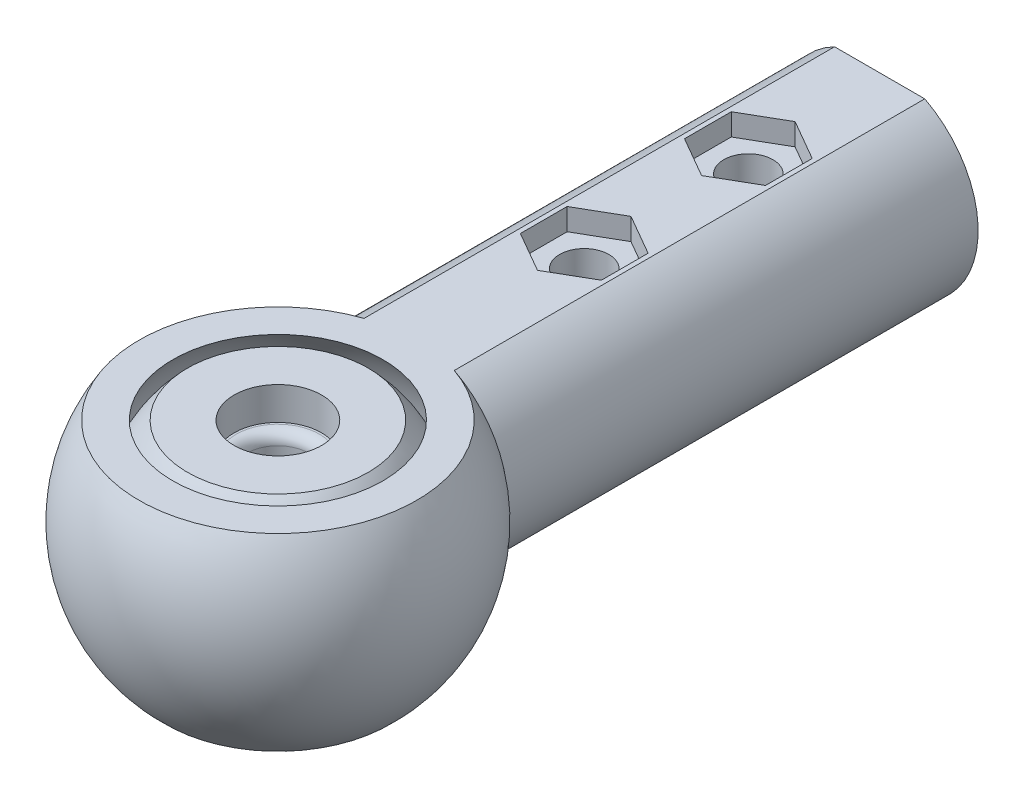
SolidWorks part; units mm, degrees
ref_plane "Front Plane" through (0, 0, 0) normal (0, 0, 1) x (1, 0, 0)
ref_plane "Top Plane" through (0, 0, 0) normal (0, 1, 0) x (1, 0, 0)
ref_plane "Right Plane" through (0, 0, 0) normal (1, 0, 0) x (0, 0, -1)
sketch "Sketch1" plane through (0, 0, 0) normal (0, 0, 1) x (1, 0, 0)
  line L0 (0, 10) -> (0, -10) construction
  line L1 (2.8, 8) -> (8.2614, 8)
  line L2 (2.8, -11) -> (3.3541, -11)
  line L3 (0, 0) -> (15, 0) construction
  line L4 (9.6047, 8) -> (12.6886, 8)
  line L5 (5.9372, -11) -> (10.198, -11)
  line L6 (2.8, 8) -> (2.8, -5.866)
  line L7 (2.8, -5.866) -> (2.8, -11)
  arc A0 (10.198, -11) -> (12.6886, 8) centre (0, 0) ccw
  arc A1 (5.9372, -11) -> (9.6047, 8) centre (0, 0) ccw
  arc A2 (3.3541, -11) -> (8.2614, 8) centre (0, 0) ccw
  dimension "D1" = 15
  dimension "D2" = 12.5
  dimension "D3" = 11.5
  dimension "D4" = 8
  dimension "D6" = 11
  dimension "D7" = 2.8
revolve "Revolve1" add sketch "Sketch1" angle 360 about L0 region at (6.5541, -0.7161, 0) region at (11.1466, 7.7895, 0)
ref_plane "Plane1" through (0, 0, -15) normal (0, 0, -1) x (-1, 0, 0)
sketch "Sketch2" plane through (0, 0, -15) normal (0, 0, -1) x (-1, 0, 0)
  line L0 (4.1231, 8) -> (-4.1231, 8)
  arc A2 (-4.1231, 8) -> (4.1231, 8) centre (0, 0) ccw
  dimension "D1" = 18
  dimension "D2" = 8
extrude "Boss-Extrude2" add sketch "Sketch2" along normal blind 40 and the other way up to next contours L0 A2 region at (0, -0.1877, -15)
sketch "Sketch3" plane through (0, 0, -55) normal (0, 0, -1) x (-1, 0, 0)
  circle A0 centre (0, 0) radius 3.05
  dimension "D1" = 6.1
extrude "Cut-Extrude1" cut sketch "Sketch3" against normal blind 35
sketch "Sketch4" plane through (0, 8, 0) normal (0, 1, 0) x (1, 0, 0)
  line L0 (0, 0) -> (0, 55) construction
  line L1 (-4.1231, 55) -> (4.1231, 55) construction
  line L3 (3.7, 40.8638) -> (3.7, 45.1362)
  line L4 (3.7, 45.1362) -> (0, 47.2724)
  line L5 (0, 47.2724) -> (-3.7, 45.1362)
  line L6 (-3.7, 45.1362) -> (-3.7, 40.8638)
  line L7 (-3.7, 40.8638) -> (0, 38.7276)
  line L8 (0, 38.7276) -> (3.7, 40.8638)
  line L9 (3.7, 25.8638) -> (3.7, 30.1362)
  line L10 (3.7, 30.1362) -> (0, 32.2724)
  line L11 (0, 32.2724) -> (-3.7, 30.1362)
  line L12 (-3.7, 30.1362) -> (-3.7, 25.8638)
  line L13 (-3.7, 25.8638) -> (0, 23.7276)
  line L14 (0, 23.7276) -> (3.7, 25.8638)
  circle A0 centre (0, 43) radius 3.7 construction
  circle A1 centre (0, 28) radius 3.7 construction
  circle A2 centre (0, 43) radius 2.25
  circle A3 centre (0, 28) radius 2.25
  dimension "D1" = 7.4
  dimension "D2" = 7.4
  dimension "D5" = 4.5
  dimension "D6" = 4.5
  dimension "D3" = 15
  dimension "D4" = 12
extrude "Cut-Extrude3" cut sketch "Sketch4" against normal blind 2 contours L13 L14 L9 L10 L11 L12 A3 | L7 L8 L3 L4 L5 L6 A2 region at (1.7935, 8, -39.8936) region at (1.7935, 8, -24.8936)
extrude "Cut-Extrude4" cut sketch "Sketch4<3>" against normal up to next contours A3 | A2 region at (0, 8, -43) region at (0, 8, -28)
sketch "Sketch4<3>" plane through (0, 8, 0) normal (0, 1, 0) x (1, 0, 0) same geometry as "Sketch4"
sketch "Sketch5" plane through (0, 8, 0) normal (0, 1, 0) x (1, 0, 0)
  circle A0 centre (0, 0) radius 4
  dimension "D1" = 8
extrude "Cut-Extrude5" cut sketch "Sketch5" against normal blind 3
fillet "Fillet1" radius 1 1 edges at (-2.8, 5, 0)
sketch "Sketch6" plane through (0, 0, -55) normal (0, 0, -1) x (-1, 0, 0)
  line L0 (0, 8.2) -> (-4.1713, 8.2)
  line L1 (4.1231, 8) -> (-4.1231, 8)
  line L2 (4.1231, 8) -> (-4.1231, 8) construction
  line L3 (0, 0) -> (7.9674, -4.6) construction
  line L4 (0, 0) -> (0, 20) construction
  line L5 (-4.8374, 20) -> (0, 20) construction
  line L6 (4.1713, 8.2) -> (-4.1713, 8.2) construction
  line L7 (-4.8374, 11.2) -> (-4.8374, 28.8)
  line L8 (10.5655, -6.1) -> (7.9674, -4.6)
  line L9 (0, 8.2) -> (4.1713, 8.2)
  line L10 (0, 11.2) -> (-4.8374, 11.2) construction
  line L11 (4.1713, 8.2) -> (4.1713, 31.8)
  line L12 (0, 31.8) -> (4.1713, 31.8)
  line L13 (0, 31.8) -> (-4.1713, 31.8)
  line L14 (10.5655, 46.1) -> (7.9674, 44.6)
  arc A0 (-4.1713, 8.2) -> (7.9674, -4.6) centre (0, 0) ccw
  arc A1 (-4.1231, 8) -> (4.1231, 8) centre (0, 0) ccw
  arc A2 (-4.1231, 8) -> (4.1231, 8) centre (0, 0) ccw construction
  arc A3 (-4.8374, 11.2) -> (10.5655, -6.1) centre (0, 0) ccw
  arc A4 (-4.1713, 8.2) -> (4.1713, 8.2) centre (0, 0) ccw construction
  arc A5 (-4.1713, 31.8) -> (7.9674, 44.6) centre (0, 40) cw
  arc A6 (-4.8374, 28.8) -> (10.5655, 46.1) centre (0, 40) cw
  point P6 (0, 0)
  point P17 (0, 0)
  point P19 (4.1713, 20)
  dimension "D3" = 20
  dimension "D4" = 120
  dimension "D1" = 0
  dimension "D2" = 0.2
  dimension "D5" = 3
